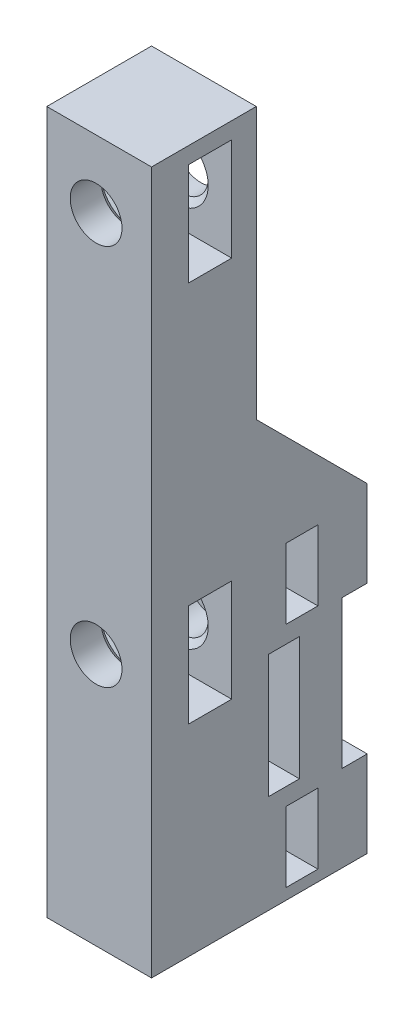
SolidWorks part; units mm, degrees
ref_plane "Plan de face" through (0, 0, 0) normal (0, 0, 1) x (1, 0, 0)
ref_plane "Plan de dessus" through (0, 0, 0) normal (0, 1, 0) x (1, 0, 0)
ref_plane "Plan de droite" through (0, 0, 0) normal (1, 0, 0) x (0, 0, -1)
sketch "Esquisse1" plane through (0, 0, 0) normal (0, 0, 1) x (1, 0, 0)
  line L0 (4, 51.5) -> (4, 20.5) construction
  line L1 (0, 0) -> (8.5, 0)
  line L2 (0, 0) -> (0, 72)
  line L3 (0, 72) -> (8.5, 72)
  line L4 (8.5, 0) -> (8.5, 72)
  circle A0 centre (4, 20.5) radius 2.1
  circle A1 centre (4, 51.5) radius 2.1
  point P9 (4, 36)
  point P10 (0, 36)
  dimension "D1" = 4.2
  dimension "D2" = 4.2
  dimension "D3" = 31
  dimension "D4" = 72
  dimension "D6" = 8.5
  dimension "D8" = 4
extrude "Boss.-Extru.1" add sketch "Esquisse1" along normal blind 17.5
sketch "Esquisse6" plane through (0, 0, 17.5) normal (0, 0, 1) x (1, 0, 0)
  line L0 (8.5, 0) -> (8.5, 72) construction
  line L1 (4, 24.6569) -> (0.4, 22.5785)
  line L2 (0.4, 22.5785) -> (0.4, 18.4215)
  line L3 (0.4, 18.4215) -> (4, 16.3431)
  line L4 (4, 16.3431) -> (7.6, 18.4215)
  line L5 (7.6, 18.4215) -> (7.6, 22.5785)
  line L6 (7.6, 22.5785) -> (4, 24.6569)
  line L7 (4, 16.3431) -> (8.5, 16.3431)
  line L8 (8.5, 16.3431) -> (8.5, 24.6569)
  line L9 (8.5, 24.6569) -> (4, 24.6569)
  circle A0 centre (4, 20.5) radius 3.6 construction
  dimension "D1" = 7.2
extrude "Enlèv. mat.-Extru.4" cut sketch "Esquisse6" against normal blind 3.5 from offset 3 offset against normal yes
sketch "Esquisse7" plane through (0, 0, 0) normal (0, 0, -1) x (-1, 0, 0)
  circle A0 centre (-4, 20.5) radius 2.1
extrude "Boss.-Extru.3" add sketch "Esquisse7" against normal blind 8
sketch "Esquisse3" plane through (0, 0, 0) normal (0, -1, 0) x (-1, 0, 0)
  line L0 (-8.5, -17.5) -> (-8.5, 0) construction
  line L1 (0, 0) -> (-8.5, 0)
  line L2 (0, 0) -> (0, -4)
  line L3 (0, -4) -> (-8.5, -4)
  line L4 (-8.5, 0) -> (-8.5, -4)
  dimension "D1" = 4
extrude "Enlèv. mat.-Extru.3" cut sketch "Esquisse3" against normal blind 19
sketch "Esquisse5" plane through (0, 0, 0) normal (0, -1, 0) x (1, 0, 0)
  line L0 (8.5, 2.0351) -> (0, 2.0351)
  line L1 (8.5, 4) -> (0, 4)
  line L2 (8.5, 4) -> (8.5, 1.7851)
  line L3 (8.5, 1.7851) -> (0, 1.7851)
  line L4 (0, 4) -> (0, 1.7851)
  line L5 (8.5, 2.7851) -> (0, 2.7851)
  line L6 (4.85, 2.0351) -> (4.85, 2.3121)
  line L7 (5.65, 2.0351) -> (5.65, 2.3121)
  circle A0 centre (5.25, 2.2301) radius 0.555
  arc A1 (5.7174, 2.5294) -> (5.8483, 2.0351) centre (4.85, 2.0351) cw
  arc A2 (4.8056, 2.5626) -> (4.6544, 2.0351) centre (5.65, 2.0351) ccw
  circle A3 centre (4.5143, 2.1851) radius 0.15
  circle A4 centre (5.9885, 2.1851) radius 0.15
  circle A5 centre (7.25, 2.2301) radius 0.555
  arc A6 (7.7174, 2.5294) -> (7.8483, 2.0351) centre (6.85, 2.0351) cw
  circle A7 centre (7.9885, 2.1851) radius 0.15
  circle A8 centre (6.5143, 2.1851) radius 0.15
  arc A9 (6.8056, 2.5626) -> (6.6544, 2.0351) centre (7.65, 2.0351) ccw
  circle A10 centre (3.25, 2.2301) radius 0.555
  arc A11 (3.7174, 2.5294) -> (3.8483, 2.0351) centre (2.85, 2.0351) cw
  circle A12 centre (3.9885, 2.1851) radius 0.15
  circle A13 centre (2.5143, 2.1851) radius 0.15
  arc A14 (2.8056, 2.5626) -> (2.6544, 2.0351) centre (3.65, 2.0351) ccw
  circle A15 centre (1.25, 2.2301) radius 0.555
  arc A16 (1.7174, 2.5294) -> (1.8483, 2.0351) centre (0.85, 2.0351) cw
  circle A17 centre (1.9885, 2.1851) radius 0.15
  circle A18 centre (0.5143, 2.1851) radius 0.15
  arc A19 (0.8056, 2.5626) -> (0.6544, 2.0351) centre (1.65, 2.0351) ccw
  circle A20 centre (-0.75, 2.2301) radius 0.555
  arc A21 (-0.2826, 2.5294) -> (-0.1517, 2.0351) centre (-1.15, 2.0351) cw
  circle A22 centre (-0.0115, 2.1851) radius 0.15
  circle A23 centre (-1.4857, 2.1851) radius 0.15
  arc A24 (-1.1944, 2.5626) -> (-1.3456, 2.0351) centre (-0.35, 2.0351) ccw
  circle A25 centre (9.25, 2.2301) radius 0.555
  circle A26 centre (8.5143, 2.1851) radius 0.15
  arc A27 (8.8056, 2.5626) -> (8.6544, 2.0351) centre (9.65, 2.0351) ccw
  arc A28 (9.7174, 2.5294) -> (9.8483, 2.0351) centre (8.85, 2.0351) cw
  circle A29 centre (9.9885, 2.1851) radius 0.15
  point P9 (4.25, 2.0351)
  point P16 (4.85, 2.1736)
  line M16 (0, 4) -> (8.5, 4)
  dimension "D2" = 1.11
  dimension "D7" = 0.3
  dimension "D8" = 0.3
  dimension "D1" = 1
  dimension "D3" = 0.75
  dimension "D4" = 0.25
  dimension "D5" = 0.4
  dimension "D6" = 0.4
  dimension "D9" = 2
  dimension "D10" = 4
  dimension "D11" = 2
extrude "Boss.-Extru.2" add sketch "Esquisse5" against normal blind 12 from offset 7 contours A26 L2 L5 A5 A6 A7 L0 | A9 A5 L5 A0 A1 A4 L0 A8 | A12 L0 A3 A2 A0 L5 A10 A11 | A17 L0 A13 A14 A10 L5 A15 A16 | A22 L4 L0 A18 A19 A15 L5 | A18 | L4 A22 | L2 A26 | A7 | A8 | A4 | A3 | A12 | L5 L2 L4 M16 | A17 | A13 offset against normal yes
sketch "Esquisse8" plane through (0, 0, 4) normal (0, 0, -1) x (-1, 0, 0)
  line L0 (-8.5, 7) -> (-8.5, 0) construction
  line L1 (0, 0) -> (-8.5, 0)
  line L2 (0, 0) -> (0, 7)
  line L3 (0, 7) -> (-8.5, 7)
  line L4 (-8.5, 0) -> (-8.5, 7)
  line L5 (0, 7) -> (-8.5, 7) construction
extrude "Boss.-Extru.4" add sketch "Esquisse8" along normal up to surface (4 mm away) up to face at (4.25, 45.5, 0)
sketch "Esquisse9" plane through (0, 0, 0) normal (0, 0, -1) x (-1, 0, 0)
  line L0 (-8.5, 0) -> (0, 0) construction
  line L1 (0, 7) -> (-8.5, 7) construction
  line L2 (0, 19) -> (-8.5, 19) construction
  circle A0 centre (-4.25, 3.75) radius 1.6
  circle A1 centre (-4.25, 22.25) radius 1.6
  point P7 (-4.25, 0)
  dimension "D1" = 3.2
  dimension "D2" = 3.2
  dimension "D3" = 3.25
  dimension "D4" = 3.25
extrude "Enlèv. mat.-Extru.5" cut sketch "Esquisse9" against normal blind 5
sketch "Esquisse10" plane through (0, 0, 0) normal (0, 0, -1) x (-1, 0, 0)
  line L0 (-5.8954, 25.1) -> (-8.5, 25.1)
  line L1 (-7.5409, 22.25) -> (-5.8954, 19.4)
  line L2 (-5.8954, 19.4) -> (-2.6046, 19.4)
  line L3 (-2.6046, 19.4) -> (-0.9591, 22.25)
  line L4 (-0.9591, 22.25) -> (-2.6046, 25.1)
  line L5 (-2.6046, 25.1) -> (-5.8954, 25.1)
  line L6 (-5.8954, 25.1) -> (-7.5409, 22.25)
  line L7 (-7.5409, 3.75) -> (-5.8954, 0.9)
  line L8 (-5.8954, 0.9) -> (-2.6046, 0.9)
  line L9 (-2.6046, 0.9) -> (-0.9591, 3.75)
  line L10 (-0.9591, 3.75) -> (-2.6046, 6.6)
  line L11 (-2.6046, 6.6) -> (-5.8954, 6.6)
  line L12 (-5.8954, 6.6) -> (-7.5409, 3.75)
  line L13 (-8.5, 19) -> (-8.5, 72) construction
  line L14 (-5.8954, 19.4) -> (-8.5, 19.4)
  line L15 (-8.5, 19.4) -> (-8.5, 25.1)
  line L16 (-5.8954, 0.9) -> (-8.5, 0.9)
  line L17 (-8.5, 0.9) -> (-8.5, 6.6)
  line L18 (-8.5, 19) -> (-8.5, 7) construction
  line L19 (-8.5, 6.6) -> (-5.8954, 6.6)
  circle A0 centre (-4.25, 22.25) radius 2.85 construction
  circle A1 centre (-4.25, 3.75) radius 2.85 construction
  circle M5 centre (-4.25, 22.25) radius 1.6
  line M9 (-8.5, 72) -> (-8.5, 19)
  dimension "D1" = 5.7
  dimension "D2" = 5.7
extrude "Enlèv. mat.-Extru.6" cut sketch "Esquisse10" against normal blind 2.6 from offset 4 contours L5 L6 L1 L2 L3 L4 M5 | L11 L12 L7 L8 L9 L10 | L19 L17 L16 L7 L12 | L14 L1 L6 L0 M9 offset against normal yes
sketch "Esquisse11" plane through (0, 0, 5) normal (0, 0, -1) x (-1, 0, 0)
  circle A0 centre (-4.25, 22.25) radius 1.6
  circle A1 centre (-4.25, 22.25) radius 1.6 construction
extrude "Enlèv. mat.-Extru.7" cut sketch "Esquisse11" against normal up to surface (1.6 mm away)
sketch "Esquisse14" plane through (8.5, 0, 0) normal (1, 0, 0) x (0, 0, -1)
  line L1 (-8, 18) -> (-5.5, 18)
  line L2 (-8, 18) -> (-8, 8)
  line L3 (-8, 8) -> (-5.5, 8)
  line L4 (-5.5, 18) -> (-5.5, 8)
  line L6 (-17.5, 0) -> (-17.5, 72) construction
  line L8 (0, 19) -> (-2.0351, 19) construction
  dimension "D1" = 2.5
  dimension "D2" = 9.5
  dimension "D3" = 10
  dimension "D4" = 1
extrude "Enlèv. mat.-Extru.9" cut sketch "Esquisse14" against normal blind 17.6
ref_plane "Plan1" through (0, 36, 0) normal (0, -1, 0) x (-1, 0, 0)
mirror "Symétrie14" about plane through (0, 36, 0) normal (0, -1, 0) of "Enlèv. mat.-Extru.9", "Enlèv. mat.-Extru.4", "Boss.-Extru.3", "Enlèv. mat.-Extru.3", "Boss.-Extru.2", "Boss.-Extru.4", "Enlèv. mat.-Extru.5", "Enlèv. mat.-Extru.6", "Enlèv. mat.-Extru.7"
chamfer "Chanfrein1" distance 0.5 angle 45 4 edges at (6.1, 20.5, 11) (6.1, 20.5, 14.5) (6.1, 51.5, 14.5) (6.1, 51.5, 11)
sketch "Esquisse15" plane through (8.5, 0, 0) normal (1, 0, 0) x (0, 0, -1)
  line L1 (0, 26) -> (-9, 26)
  line L2 (0, 26) -> (0, 72)
  line L3 (0, 72) -> (-9, 72)
  line L4 (-9, 26) -> (-9, 72)
  line L5 (-9, 57) -> (-17.5, 57)
  line L6 (-17.5, 0) -> (-17.5, 72) construction
  line L7 (-17.5, 0) -> (0, 0) construction
  line L8 (-17.5, 72) -> (0, 72) construction
  line M4 (-6.6, 46.9) -> (-6.6, 52.6)
  line M5 (-6.6, 52.6) -> (-4, 52.6)
  line M6 (-4, 52.6) -> (-4, 46.9)
  line M7 (-4, 46.9) -> (-6.6, 46.9)
  line M28 (0, 65) -> (0, 72)
  line M29 (0, 72) -> (-17.5, 72)
  line M30 (-17.5, 72) -> (-17.5, 0)
  line M36 (0, 19) -> (0, 53)
  line M37 (0, 53) -> (-2.0351, 53)
  line M38 (-2.0351, 53) -> (-2.0351, 65)
  line M39 (-2.0351, 65) -> (0, 65)
  line M40 (-6.6, 65.4) -> (-6.6, 71.1)
  line M41 (-6.6, 71.1) -> (-4, 71.1)
  line M42 (-4, 71.1) -> (-4, 65.4)
  line M43 (-4, 65.4) -> (-6.6, 65.4)
  line M44 (-8, 54) -> (-8, 64)
  line M45 (-8, 64) -> (-5.5, 64)
  line M46 (-5.5, 64) -> (-5.5, 54)
  line M47 (-5.5, 54) -> (-8, 54)
  dimension "D1" = 9
  dimension "D2" = 26
  dimension "D3" = 15
extrude "Enlèv. mat.-Extru.10" cut sketch "Esquisse15" against normal blind 10 contours L4 L1 M36 M37 M38 M39 M28 M29 M43 M40 M41 M42 M47 M44 M45 M46 M7 M4 M5 M6 | L5 L4 M29 M30
chamfer "Chanfrein2" distance 9 angle 45 1 edges at (4.25, 26, 9)
